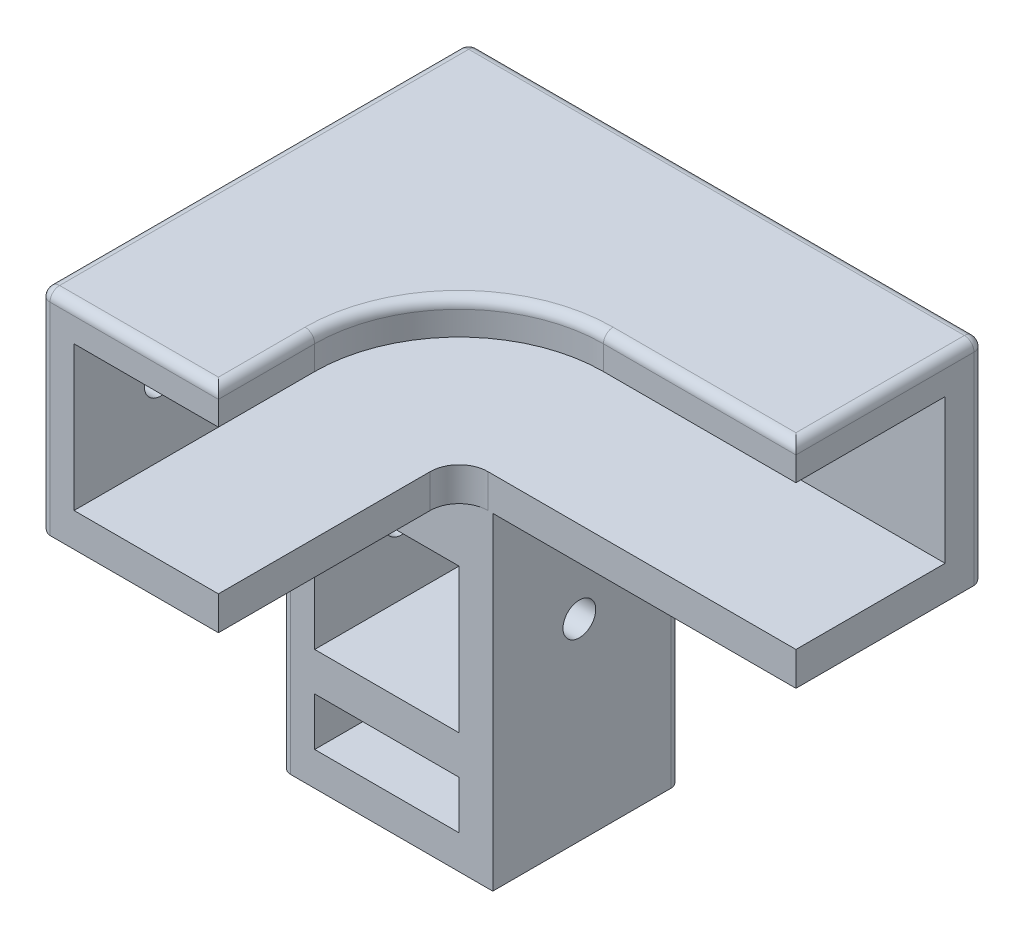
SolidWorks part; units mm, degrees
ref_plane "Front Plane" through (0, 0, 0) normal (0, 0, 1) x (1, 0, 0)
ref_plane "Top Plane" through (0, 0, 0) normal (0, 1, 0) x (1, 0, 0)
ref_plane "Right Plane" through (0, 0, 0) normal (1, 0, 0) x (0, 0, -1)
sketch "Sketch1" plane through (0, 0, 0) normal (0, 0, 1) x (1, 0, 0)
  line L1 (-5.6994, 32.9163) -> (16.3006, 32.9163)
  line L2 (-5.6994, 10.9163) -> (-5.6994, -23.0837)
  line L3 (-5.6994, -23.0837) -> (16.3006, -23.0837)
  line L4 (16.3006, 32.9163) -> (16.3006, -23.0837)
  line L5 (-5.6994, 10.9163) -> (-37.1994, 10.9163)
  line L7 (-5.6994, 32.9163) -> (-37.1994, 32.9163)
  line L8 (-37.1994, 10.9163) -> (-37.1994, 32.9163)
  dimension "D1" = 22
  dimension "D2" = 22
  dimension "D3" = 56
  dimension "D4" = 53.5
extrude "Boss-Extrude1" add sketch "Sketch1" along normal blind 19.5
sketch "Sketch3" plane through (0, 0, 19.5) normal (0, 0, 1) x (1, 0, 0)
  line L1 (16.3006, 32.9163) -> (-2.1994, 32.9163)
  line L2 (16.3006, 32.9163) -> (16.3006, 10.9163)
  line L3 (16.3006, 10.9163) -> (-2.1994, 10.9163)
  line L4 (-2.1994, 32.9163) -> (-2.1994, 10.9163)
  dimension "D1" = 18.5
extrude "Boss-Extrude2" add sketch "Sketch3" along normal blind 25
sketch "Sketch5" plane through (0, 0, 44.5) normal (0, 0, 1) x (1, 0, 0)
  line L0 (-37.1994, 32.9163) -> (-37.1994, 10.9163) construction
  line L1 (-37.1994, 29.4163) -> (12.8006, 29.4163)
  line L2 (-37.1994, 29.4163) -> (-37.1994, 14.4163)
  line L3 (-37.1994, 14.4163) -> (12.8006, 14.4163)
  line L4 (12.8006, 29.4163) -> (12.8006, 14.4163)
  line L5 (16.3006, 10.9163) -> (16.3006, 32.9163) construction
  line L6 (-2.1994, 4.4163) -> (12.8006, 4.4163)
  line L7 (-2.1994, 4.4163) -> (-2.1994, -10.5837)
  line L8 (-2.1994, -10.5837) -> (12.8006, -10.5837)
  line L9 (12.8006, 4.4163) -> (12.8006, -10.5837)
  line L12 (-2.1994, 32.9163) -> (-37.1994, 32.9163) construction
  line L13 (-2.1994, 10.9163) -> (16.3006, 10.9163) construction
  line L15 (16.3006, -23.0837) -> (16.3006, 10.9163) construction
  line L16 (-5.6994, -23.0837) -> (16.3006, -23.0837) construction
  line L17 (-2.1994, -14.5837) -> (12.8006, -14.5837)
  line L18 (-2.1994, -14.5837) -> (-2.1994, -19.5837)
  line L19 (-2.1994, -19.5837) -> (12.8006, -19.5837)
  line L20 (12.8006, -14.5837) -> (12.8006, -19.5837)
  dimension "D1" = 3.5
  dimension "D2" = 6.5
  dimension "D3" = 15
  dimension "D4" = 3.5
  dimension "D5" = 15
  dimension "D6" = 15
  dimension "D7" = 3.5
  dimension "D8" = 15
  dimension "D9" = 4
  dimension "D10" = 3.5
extrude "Cut-Extrude1" cut sketch "Sketch5" against normal offset from surface (40.5 mm away) 4 up to face at (-8.8661, 6.9163, 0)
sketch "Sketch7" plane through (16.3006, 0, 0) normal (1, 0, 0) x (0, 0, -1)
  line L0 (-34.5, 10.9163) -> (-19.5, 10.9163)
  line L1 (-44.5, 10.9163) -> (-19.5, 10.9163) construction
  line L2 (-19.5, 10.9163) -> (-19.5, -4.0837)
  line L3 (-19.5, -23.0837) -> (-19.5, 10.9163) construction
  arc A0 (-34.5, 10.9163) -> (-19.5, -4.0837) centre (-34.5, -4.0837) cw
  dimension "D1" = 15
extrude "Boss-Extrude4" add sketch "Sketch7" against normal blind 3.5
sketch "Sketch8" plane through (0, 0, 0) normal (0, 0, -1) x (-1, 0, 0)
  line L0 (5.6994, 10.9163) -> (20.6994, 10.9163)
  line L1 (37.1994, 10.9163) -> (5.6994, 10.9163) construction
  line L2 (5.6994, 10.9163) -> (5.6994, -4.0837)
  line L3 (5.6994, 10.9163) -> (5.6994, -23.0837) construction
  arc A0 (20.6994, 10.9163) -> (5.6994, -4.0837) centre (20.6994, -4.0837) ccw
  dimension "D1" = 15
extrude "Boss-Extrude5" add sketch "Sketch8" against normal blind 3.5
sketch "Sketch9" plane through (0, 32.9163, 0) normal (0, 1, 0) x (1, 0, 0)
  line L0 (-2.1994, -34.5) -> (-2.1994, -19.5)
  line L1 (-2.1994, -44.5) -> (-2.1994, -19.5) construction
  line L2 (-2.1994, -19.5) -> (-17.1994, -19.5)
  line L3 (-2.1994, -19.5) -> (-37.1994, -19.5) construction
  arc A0 (-2.1994, -34.5) -> (-17.1994, -19.5) centre (-17.1994, -34.5) ccw
  dimension "D1" = 15
extrude "Boss-Extrude6" add sketch "Sketch9" against normal blind 3.5
fillet "Fillet3" radius 3 1 edges
sketch "Sketch11" plane through (0, 0, 0) normal (0, 0, -1) x (-1, 0, 0)
  line L0 (1.1994, -23.0837) -> (1.1994, 10.9163) construction
  line L2 (5.6994, -23.0837) -> (-16.3006, -23.0837) construction
  line L5 (5.6994, -4.0837) -> (5.6994, -23.0837) construction
  text T0 "MR.3" font "Century Gothic" height 12
  dimension "D1" = 4.5
extrude "Cut-Extrude3" cut sketch "Sketch11" against normal blind 1
sketch "Sketch12" plane through (0, 0, 0) normal (0, 0, -1) x (-1, 0, 0)
  line L0 (37.1994, 21.9163) -> (-16.3006, 21.9163) construction
  line L1 (37.1994, 32.9163) -> (37.1994, 10.9163) construction
  line L2 (-16.3006, -23.0837) -> (-16.3006, 32.9163) construction
  line L3 (-12.8006, 14.4163) -> (-12.8006, 29.4163) construction
  circle A0 centre (-5.3006, 21.9163) radius 1.7
  circle A1 centre (10.9494, 21.9163) radius 1.7
  circle A2 centre (27.1994, 21.9163) radius 1.7
  dimension "D4" = 3.4
  dimension "D1" = 7.5
  dimension "D2" = 10
  dimension "D3" = 16.25
extrude "Cut-Extrude4" cut sketch "Sketch12" against normal blind 5
sketch "Sketch13" plane through (-5.6994, 0, 0) normal (-1, 0, 0) x (0, 0, 1)
  line L0 (4, 4.4163) -> (19.5, 4.4163) construction
  line L1 (19.5, 10.9163) -> (19.5, -23.0837) construction
  circle A0 centre (10.5, -3.0837) radius 1.7
  dimension "D2" = 9
  dimension "D3" = 3.4
  dimension "D1" = 7.5
extrude "Cut-Extrude5" cut sketch "Sketch13" against normal blind 45
sketch "Sketch14" plane through (16.3006, 0, 0) normal (1, 0, 0) x (0, 0, -1)
  line L0 (-10.5, -3.0837) -> (-10.5, 32.9163) construction
  line L1 (-44.5, 32.9163) -> (0, 32.9163) construction
  line L2 (-44.5, 21.9163) -> (-10.5, 21.9163) construction
  line L3 (-44.5, 10.9163) -> (-44.5, 32.9163) construction
  circle A0 centre (-10.5, 21.9163) radius 1.7
  circle A1 centre (-35.5, 21.9163) radius 1.7
  dimension "D1" = 3.4
  dimension "D2" = 9
extrude "Cut-Extrude6" cut sketch "Sketch14" against normal blind 45
sketch "Sketch15" plane through (0, -23.0837, 0) normal (0, -1, 0) x (1, 0, 0)
  line L0 (16.3006, 9.75) -> (-5.6994, 9.75) construction
  line L1 (16.3006, 19.5) -> (16.3006, 0) construction
  line L2 (-5.6994, 19.5) -> (-5.6994, 0) construction
  line L3 (5.3006, 19.5) -> (5.3006, 0) construction
  line L4 (-5.6994, 19.5) -> (16.3006, 19.5) construction
  line L5 (-5.6994, 0) -> (16.3006, 0) construction
  circle A0 centre (5.3006, 9.75) radius 1.7
  dimension "D1" = 3.4
extrude "Cut-Extrude7" cut sketch "Sketch15" against normal blind 4
mirror "Mirror2" about plane through (16.3006, 32.9163, 19.5) normal (-1, 0, 0) of "Cut-Extrude7", "Cut-Extrude6", "Cut-Extrude5", "Cut-Extrude4", "Fillet3", "Boss-Extrude6", "Boss-Extrude5", "Boss-Extrude4", "Cut-Extrude1", "Boss-Extrude2", "Boss-Extrude1"
sketch "Sketch16" plane through (0, 0, 0) normal (0, 0, -1) x (-1, 0, 0)
  line L0 (-69.8006, 32.9163) -> (37.1994, 32.9163) construction
  line L1 (-16.3006, 32.9163) -> (53.9943, 32.9163)
  line L2 (-16.3006, 32.9163) -> (-16.3006, -24.95)
  line L3 (-16.3006, -24.95) -> (53.9943, -24.95)
  line L4 (53.9943, 32.9163) -> (53.9943, -24.95)
extrude "Cut-Extrude8" cut sketch "Sketch16" against normal blind 72
sketch "Sketch20" plane through (0, 0, 0) normal (0, 0, -1) x (-1, 0, 0)
  line L0 (-22.3006, -23.0837) -> (-22.3006, 16.9163) construction
  line L1 (-16.3006, -23.0837) -> (-38.3006, -23.0837) construction
  line L2 (-16.3006, 32.9163) -> (-16.3006, -23.0837) construction
  text T0 "ALFR3D" font "Murder Of Mayday" height 10
  dimension "D1" = 6
  dimension "D2" = 40
extrude "Cut-Extrude9" [suppressed] cut sketch "Sketch20" against normal blind 1
fillet "Fillet4" radius 1 16 edges at (16.3006, 10.9163, 39.5) (16.3006, 6.5229, 23.8934) (61.5506, 10.9163, 0) (42.694, 6.5229, 0) (34.8006, 32.9163, 39.5) (39.194, 32.9163, 23.8934) (16.3006, -13.5837, 19.5) (38.3006, -13.5837, 0) (16.3006, 4.9163, 0) (43.0506, 32.9163, 0) (16.3006, 32.9163, 22.25) (16.3006, 21.9163, 44.5) (69.8006, 21.9163, 0) (69.8006, 32.9163, 9.75) (25.5506, 32.9163, 44.5)
